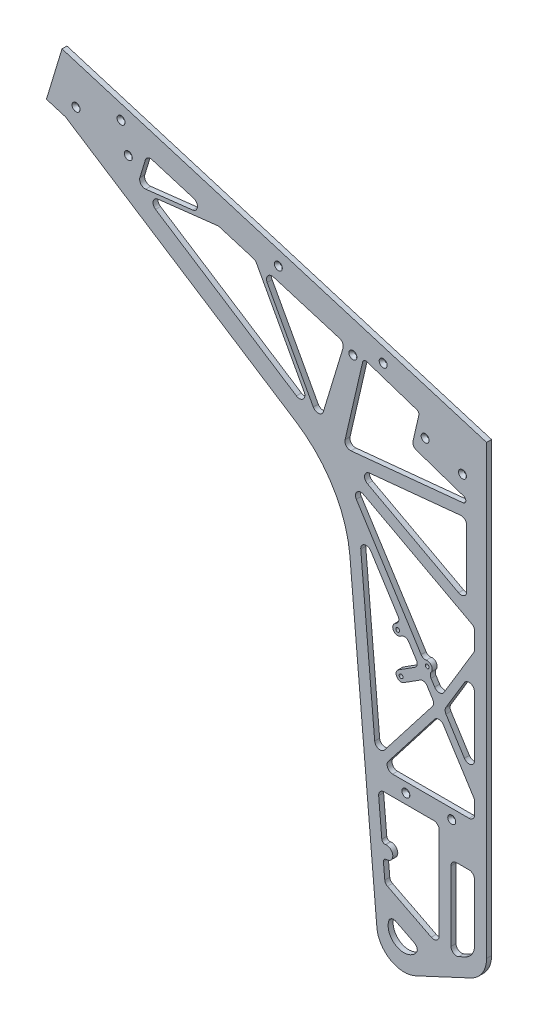
SolidWorks part; units mm, degrees
material "Beech"
ref_plane "Front Plane" through (0, 0, 0) normal (0, 0, 1) x (1, 0, 0)
ref_plane "Top Plane" through (0, 0, 0) normal (0, 1, 0) x (1, 0, 0)
ref_plane "Right Plane" through (0, 0, 0) normal (1, 0, 0) x (0, 0, -1)
sketch "Sketch2" plane through (0, 0, 0) normal (0, 0, 1) x (1, 0, 0)
  line L3 (52.061, -347.2658) -> (17.0528, -329.4943)
  line L18 (0.7275, -204.3995) -> (4.7586, -250.4747)
  line L19 (71, -196.7894) -> (7.7009, -196.7894)
  line L20 (78, -320.9929) -> (78, -203.7894)
  line L21 (8.8549, -297.2958) -> (67.8314, -327.2347)
  line L22 (6.8503, -274.3834) -> (8.8549, -297.2958)
  line L23 (11.4827, -269.9628) -> (10.4865, -270.05)
  line L24 (9.092, -254.1109) -> (10.0882, -254.0237)
  line L27 (123, -309.0696) -> (123, -235.7894)
  line L28 (102.9583, -331.1566) -> (111.4524, -327.1958)
  line L29 (93, -235.7894) -> (93, -324.8124)
  line L30 (116, -228.7894) -> (100, -228.7894)
  line L35 (123, -164.7894) -> (123, -147.491)
  line L36 (18.4936, -171.7894) -> (116, -171.7894)
  line L37 (71.9182, -84.5103) -> (12.9629, -160.4984)
  line L38 (123, -147.491) -> (83.3585, -85.0495)
  line L41 (123, -104.7468) -> (123, -28.6549)
  line L42 (86.5792, -71.4649) -> (110.0903, -108.4986)
  line L43 (110.0027, -25.0448) -> (86.4916, -64.103)
  line L47 (-22.0887, 56.3913) -> (-4.3233, -146.6681)
  line L48 (69.6883, -63.5168) -> (-9.2057, 60.7532)
  line L49 (8.1807, -150.3489) -> (69.3092, -71.5595)
  line L55 (84.1071, -48.674) -> (123, 15.9373)
  line L56 (-27.7256, 108.5825) -> (72.2002, -48.8158)
  line L57 (123, 42.7347) -> (-18.5117, 118.5054)
  line L58 (123, 15.9373) -> (123, 42.7347)
  line L61 (105.3136, 157.4535) -> (-10.9295, 145.9995)
  line L62 (113, 76.7923) -> (113, 150.4873)
  line L63 (-13.5473, 132.8622) -> (102.6958, 70.6213)
  line L71 (49.3928, 246.173) -> (-14.4833, 267.3378)
  line L72 (43.1791, 203.129) -> (52.0322, 241.4762)
  line L73 (109.2468, 180.5917) -> (43.1791, 203.129)
  line L74 (-34.5621, 158.7435) -> (108.3476, 172.8251)
  line L75 (-19.6388, 264.4406) -> (-42.0691, 167.2844)
  line L99 (-35.9297, 42.1538) -> (-1.5139, -351.2208)
  line L100 (48.0382, -379.8296) -> (118.2139, -347.1062)
  line L101 (138.3789, -315.4534) -> (138.3789, 254.5381)
  line L102 (138.3789, 254.5381) -> (-403.0991, 418.4193)
  line L103 (-403.0991, 418.4193) -> (-422.935, 352.8794)
  line L104 (-422.935, 352.8794) -> (-398.6241, 345.5216)
  line L105 (-398.6241, 345.5216) -> (-105.0266, 156.03)
  line L106 (-35.9297, 42.1538) -> (-1.5139, -351.2208)
  line L107 (48.0382, -379.8296) -> (118.2139, -347.1062)
  line L108 (138.3789, -315.4534) -> (138.3789, 254.5381)
  line L109 (138.3789, 254.5381) -> (-403.0991, 418.4193)
  line L110 (-403.0991, 418.4193) -> (-422.935, 352.8794)
  line L111 (-422.935, 352.8794) -> (-398.6241, 345.5216)
  line L112 (-398.6241, 345.5216) -> (-105.0266, 156.03)
  arc A2 (17.0528, -329.4943) -> (52.061, -347.2658) centre (32.8243, -341.7931) ccw
  arc A14 (4.7586, -250.4747) -> (9.092, -254.1109) centre (8.7434, -250.1261) ccw
  arc A15 (7.7009, -196.7894) -> (0.7275, -204.3995) centre (7.7009, -203.7894) ccw
  arc A16 (78, -203.7894) -> (71, -196.7894) centre (71, -203.7894) ccw
  arc A17 (67.8314, -327.2347) -> (78, -320.9929) centre (71, -320.9929) ccw
  arc A18 (10.4865, -270.05) -> (6.8503, -274.3834) centre (10.8351, -274.0347) ccw
  arc A19 (11.4827, -269.9628) -> (10.0882, -254.0237) centre (10.7854, -261.9933) ccw
  arc A22 (123, -235.7894) -> (116, -228.7894) centre (116, -235.7894) ccw
  arc A23 (111.4524, -327.1958) -> (123, -309.0696) centre (103, -309.0696) ccw
  arc A24 (93, -324.8124) -> (102.9583, -331.1566) centre (100, -324.8124) ccw
  arc A25 (100, -228.7894) -> (93, -235.7894) centre (100, -235.7894) ccw
  arc A28 (116, -171.7894) -> (123, -164.7894) centre (116, -164.7894) ccw
  arc A29 (12.9629, -160.4984) -> (18.4936, -171.7894) centre (18.4936, -164.7894) ccw
  arc A30 (83.3585, -85.0495) -> (71.9182, -84.5103) centre (77.4488, -88.8013) ccw
  arc A34 (110.0903, -108.4986) -> (123, -104.7468) centre (116, -104.7468) ccw
  arc A35 (86.4916, -64.103) -> (86.5792, -71.4649) centre (92.4888, -67.7131) ccw
  arc A36 (123, -28.6549) -> (110.0027, -25.0448) centre (116, -28.6549) ccw
  arc A40 (-4.3233, -146.6681) -> (8.1807, -150.3489) centre (2.65, -146.058) ccw
  arc A41 (-9.2057, 60.7532) -> (-22.0887, 56.3913) centre (-15.1153, 57.0014) ccw
  arc A42 (69.3092, -71.5595) -> (69.6883, -63.5168) centre (63.7786, -67.2686) ccw
  arc A44 (72.2002, -48.8158) -> (84.1071, -48.674) centre (78.1098, -45.064) ccw
  arc A45 (-18.5117, 118.5054) -> (-27.7256, 108.5825) centre (-21.8159, 112.3343) ccw
  arc A50 (113, 150.4873) -> (105.3136, 157.4535) centre (106, 150.4873) ccw
  arc A51 (102.6958, 70.6213) -> (113, 76.7923) centre (106, 76.7923) ccw
  arc A52 (-10.9295, 145.9995) -> (-13.5473, 132.8622) centre (-10.2431, 139.0332) ccw
  arc A58 (-14.4833, 267.3378) -> (-19.6388, 264.4406) centre (-15.7414, 263.5408) ccw
  arc A59 (52.0322, 241.4762) -> (49.3928, 246.173) centre (48.1347, 242.376) ccw
  arc A60 (108.3476, 172.8251) -> (109.2468, 180.5917) centre (107.9554, 176.8059) ccw
  arc A61 (-42.0691, 167.2844) -> (-34.5621, 158.7435) centre (-35.2485, 165.7098) ccw
  arc A77 (-35.9297, 42.1538) -> (-105.0266, 156.03) centre (-187.6695, 27.9835) ccw
  arc A78 (-1.5139, -351.2208) -> (48.0382, -379.8296) centre (33.2782, -348.1768) ccw
  arc A79 (118.2139, -347.1062) -> (138.3789, -315.4534) centre (103.4539, -315.4534) ccw
  arc A80 (-35.9297, 42.1538) -> (-105.0266, 156.03) centre (-187.6695, 27.9835) ccw
  arc A81 (-1.5139, -351.2208) -> (48.0382, -379.8296) centre (33.2782, -348.1768) ccw
  arc A82 (118.2139, -347.1062) -> (138.3789, -315.4534) centre (103.4539, -315.4534) ccw
  line B0 (-69.7843, 184.37) -> (-44.7069, 267.0652)
  line B1 (-141.4417, 291.191) -> (-82.6325, 183.0571)
  line B2 (-49.3742, 275.7954) -> (-133.2609, 301.2341)
  line B3 (-94.2196, 193.8972) -> (-156.4138, 308.2553)
  line B4 (-283.8496, 300.7813) -> (-104.1681, 184.6735)
  line B5 (-203.4472, 322.5182) -> (-280.8504, 313.6148)
  line B6 (-156.4138, 308.2553) -> (-203.4472, 322.5182)
  line B7 (-235.2905, 337.3996) -> (-288.1216, 353.4207)
  line B8 (-296.2966, 316.871) -> (-236.522, 323.7467)
  line B9 (-296.8518, 348.7534) -> (-303.7953, 325.8566)
  arc B10 (-44.7069, 267.0652) -> (-49.3742, 275.7954) centre (-51.4056, 269.0966) ccw
  arc B11 (-82.6325, 183.0571) -> (-69.7843, 184.37) centre (-76.4831, 186.4014) ccw
  arc B12 (-133.2609, 301.2341) -> (-141.4417, 291.191) centre (-135.2923, 294.5354) ccw
  arc B13 (-104.1681, 184.6735) -> (-94.2196, 193.8972) centre (-100.369, 190.5528) ccw
  arc B14 (-280.8504, 313.6148) -> (-283.8496, 300.7813) centre (-280.0505, 306.6606) ccw
  arc B15 (-236.522, 323.7467) -> (-235.2905, 337.3996) centre (-237.3219, 330.7009) ccw
  arc B16 (-303.7953, 325.8566) -> (-296.2966, 316.871) centre (-297.0965, 323.8251) ccw
  arc B17 (-288.1216, 353.4207) -> (-296.8518, 348.7534) centre (-290.153, 346.7219) ccw
  dimension "D13" = 0
sketch_block_instance "Block1-1"
sketch_block "Block1" parameters "D4"=7, "D1"=23.432, "D2"=23.9265, "D3"=55.2069
extrude "Boss-Extrude1" add sketch "Sketch2" along normal blind 6.35
sketch "Sketch3" plane through (0, 0, 6.35) normal (0, 0, 1) x (1, 0, 0)
  line L25 (32.2931, -4.6137) -> (25.0263, -9.2271) construction
  line L26 (69.6883, -63.5168) -> (-9.2057, 60.7532) construction
  line L27 (35.6965, -9.9746) -> (28.4297, -14.588)
  line L28 (28.8896, 0.7472) -> (21.6228, -3.8662)
  line L29 (29.3174, -58.2747) -> (55.7191, -41.5133) construction
  line L30 (25.914, -52.9138) -> (52.3157, -36.1524)
  line L31 (32.7208, -63.6356) -> (59.1225, -46.8742)
  line L32 (62.6488, -30.6471) -> (61.2353, -31.5444) construction
  line L33 (-27.7256, 108.5825) -> (72.2002, -48.8158) construction
  line L34 (66.0522, -36.008) -> (64.6387, -36.9053)
  line L35 (59.2454, -25.2862) -> (57.8319, -26.1835)
  arc A13 (35.6965, -9.9746) -> (28.8896, 0.7472) centre (32.2931, -4.6137) ccw
  arc A14 (21.6228, -3.8662) -> (28.4297, -14.588) centre (25.0263, -9.2271) ccw
  arc A15 (25.914, -52.9138) -> (32.7208, -63.6356) centre (29.3174, -58.2747) ccw
  arc A16 (59.1225, -46.8742) -> (52.3157, -36.1524) centre (55.7191, -41.5133) ccw
  arc A17 (66.0522, -36.008) -> (59.2454, -25.2862) centre (62.6488, -30.6471) ccw
  arc A18 (57.8319, -26.1835) -> (64.6387, -36.9053) centre (61.2353, -31.5444) ccw
  point P6 (28.6597, -6.9204)
  point P13 (42.5182, -49.894)
  point P20 (61.942, -31.0957)
  dimension "D2" = 6.35
extrude "Boss-Extrude3" add sketch "Sketch3" against normal through all contours A18 A16 L30 A15 L31 | L35 A18 A16 L34 A17 | L28 A14 L27 A13 region at (28.6597, -6.9204, 6.35) region at (42.3663, -50.0213, 6.35) region at (62.0617, -30.908, 6.35)
fillet "Fillet2" radius 6.35 15 edges at (-203.4472, 322.5182, 3.175) (-156.4138, 308.2553, 3.175) (43.1791, 203.129, 3.175) (123, 42.7347, 3.175) (123, 15.9373, 3.175) (123, -147.491, 3.175) (8.8549, -297.2958, 3.175) (17.0528, -329.4943, 3.175) (52.061, -347.2658, 3.175) (64.6387, -36.9053, 3.175) (57.8319, -26.1835, 3.175) (28.8896, 0.7472, 3.175) (35.6965, -9.9746, 3.175) (52.3157, -36.1524, 3.175) (59.1225, -46.8742, 3.175)
hole_wizard "#8 Clearance Hole1" positions "Sketch4" profile "Sketch5" hole size "#8" standard "ANSI Inch" end condition up to next
sketch "Sketch4" plane through (0, 0, 6.35) normal (0, 0, 1) x (1, 0, 0)
  circle A0 centre (25.0263, -9.2271) radius 2.4574 construction
  circle A1 centre (29.3174, -58.2747) radius 2.4574 construction
  circle A2 centre (62.6488, -30.6471) radius 2.4574 construction
  point P0 (62.6488, -30.6471)
  point P2 (29.3174, -58.2747)
  point P4 (25.0263, -9.2271)
sketch "Sketch5" plane through (62.6488, -30.6471, 6.35) normal (1, 0, 0) x (0, -1, 0)
  line L0 (0, 0) -> (0, 6.35)
  line L1 (0, 6.35) -> (2.4574, 6.35)
  line L2 (2.4574, 6.35) -> (2.4574, 0)
  line L5 (2.4574, 0) -> (0, 0)
  line L11 (0, -6.35) -> (0, 107.95) construction
  dimension "Thru Hole Dia." = 4.9149
  dimension "Thru Hole Depth" = 6.35
hole_wizard "Hole1" positions "Sketch6" profile "Sketch7" legacy
sketch "Sketch6" plane through (280.9657, -208.179, 6.35) normal (0, 0, 1) x (-0.09, 0.9959, 0)
  line L0 (47.5949, 261.3648) -> (37.7623, 152.508) construction
  line L6 (451.4691, 193.1171) -> (418.4769, 118.1196) construction
  line L11 (486.2923, 274.2447) -> (514.0528, 264.0879) construction
  line L16 (472.4376, 447.6352) -> (491.8067, 432.4853) construction
  line L19 (635.9114, 629.7221) -> (595.5648, 529.8608) construction
  line L24 (664.0363, 618.3589) -> (454.7061, 100.2486) construction
  line L28 (664.0363, 618.3589) -> (611.7037, 488.8313)
  line L29 (611.7037, 488.8313) -> (559.3712, 359.3037)
  line L30 (559.3712, 359.3037) -> (507.0387, 229.7761)
  line L31 (507.0387, 229.7761) -> (454.7061, 100.2486)
  point P12 (45.8811, 242.3921)
  point P14 (40.6185, 184.1293)
  point P29 (426.1478, 135.557)
  point P31 (446.3552, 181.4922)
  point P48 (500.1726, 269.1663)
  point P79 (628.7751, 612.0592)
  point P81 (602.701, 547.5236)
  point P98 (559.3712, 359.3037)
  point P100 (507.0387, 229.7761)
  point P112 (637.87, 553.5951)
  point P120 (0, 0)
  dimension "D1" = 19.05
  dimension "D2" = 31.75
  dimension "D3" = 12.7
  dimension "D4" = 19.05
  dimension "D5" = 19.05
  dimension "D6" = 19.05
sketch "Sketch7" plane through (-327.7674, 377.3035, 6.35) normal (1, 0, 0) x (0, -1, 0)
  line L0 (0, 0) -> (0, 32.7039)
  line L1 (0, 32.7039) -> (1.5875, 31.75)
  line L2 (1.5875, 31.75) -> (1.5875, 4.0177)
  line L3 (1.5875, 4.0177) -> (5.08, 0)
  line L4 (5.08, 0) -> (0, 0)
  line L5 (0, -14.3089) -> (0, 102.4216) construction
  line L6 (0, 32.7039) -> (-1.5875, 31.75) construction
  line L7 (-1.5875, 4.0177) -> (-5.08, 0) construction
  dimension "Diameter" = 3.175
  dimension "Depth" = 31.75
  dimension "C-Sink Diameter" = 10.16
  dimension "C-Sink Angle" = 82
  dimension "Drill Angle" = 118
